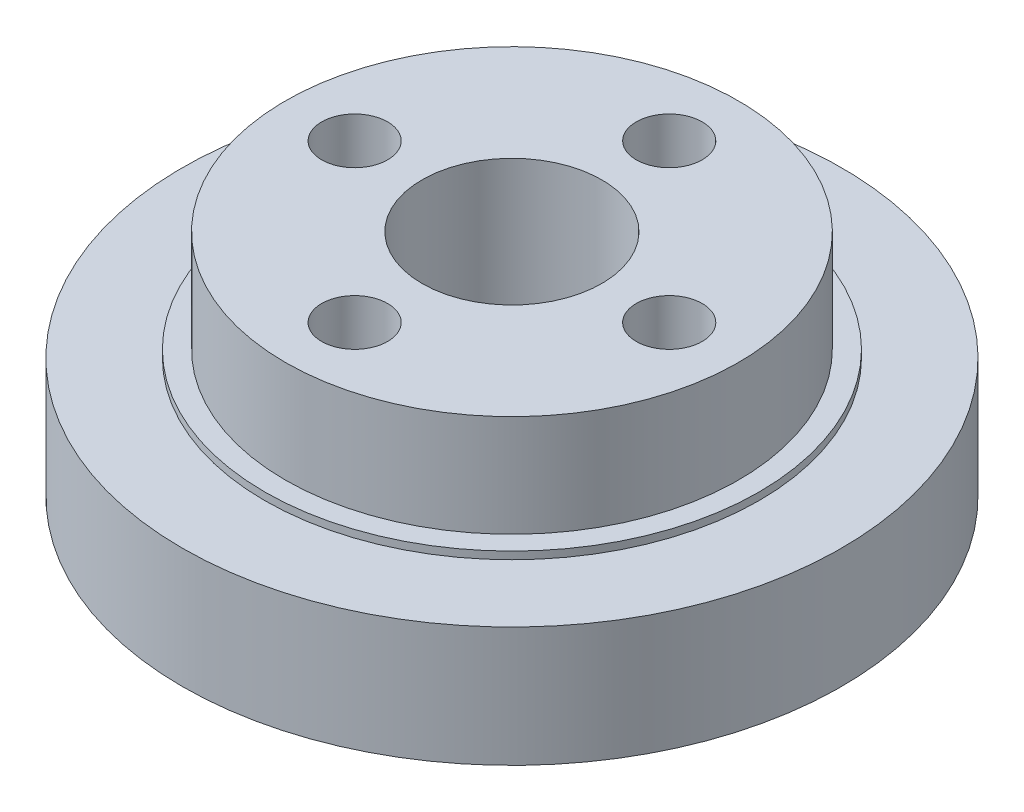
SolidWorks part; units mm, degrees
ref_plane "Front Plane" through (0, 0, 0) normal (0, 0, 1) x (1, 0, 0)
ref_plane "Top Plane" through (0, 0, 0) normal (0, 1, 0) x (1, 0, 0)
ref_plane "Right Plane" through (0, 0, 0) normal (1, 0, 0) x (0, 0, -1)
sketch "Sketch1" plane through (0, 0, 0) normal (0, 1, 0) x (1, 0, 0)
  circle A0 centre (0, 0) radius 22
  dimension "D1" = 44
extrude "Boss-Extrude1" add sketch "Sketch1" along normal blind 8
sketch "Sketch2" plane through (0, 8, 0) normal (0, 1, 0) x (1, 0, 0)
  circle A0 centre (0, 0) radius 16.5
  dimension "D1" = 33
extrude "Boss-Extrude2" add sketch "Sketch2" along normal blind 0.5
sketch "Sketch3" plane through (0, 8.5, 0) normal (0, 1, 0) x (1, 0, 0)
  circle A0 centre (0, 0) radius 15.125
  dimension "D1" = 30.25
extrude "Boss-Extrude3" add sketch "Sketch3" along normal blind 6.8
sketch "Sketch4" plane through (0, 15.3, 0) normal (0, 1, 0) x (1, 0, 0)
  circle A0 centre (0, 0) radius 6
  dimension "D1" = 12
extrude "Cut-Extrude1" cut sketch "Sketch4" against normal through all
sketch "Sketch5" plane through (0, 0, 0) normal (0, 1, 0) x (1, 0, 0)
  line L0 (0, 0) -> (26.2686, 0) construction
  line L1 (-8.415, 0) -> (8.415, 0) construction
  line L2 (0, 0) -> (26.9941, 4.2754) construction
  circle A0 centre (18.2722, 2.894) radius 1.6
  dimension "D2" = 3.2
  dimension "D1" = 9
  dimension "D3" = 18.5
extrude "Cut-Extrude2" cut sketch "Sketch5" along normal blind 7
pattern_circular "CirPattern1" count 6 over 360 about axis through (0, 8, 0) along (0, -1, 0) of "Cut-Extrude2" reverse direction yes
sketch "Sketch6" plane through (0, 15.3, 0) normal (0, 1, 0) x (1, 0, 0)
  line L0 (-8.415, 0) -> (8.415, 0) construction
  circle A0 centre (10.5, 0) radius 2.2
  dimension "D1" = 4.4
  dimension "D2" = 10.5
extrude "Cut-Extrude3" cut sketch "Sketch6" against normal blind 5.5
pattern_circular "CirPattern2" count 4 over 360 about axis through (0, 8, 0) along (0, -1, 0) of "Cut-Extrude3"
equation "\"pin_circle_R\" = 27"
equation "\"ecc\" = 1.5"
equation "\"n_pins\" = 11"
equation "\"pin_d\" = 3"
equation "\"out_pin_R\" = 18.5"
equation "\"disc_clr\" = 0.1"
equation "\"seat_6803\" = 26.1"
equation "\"disc_t\" = 5"
equation "\"out_hole_clr\" = 0.5"
equation "\"boss_17\" = 17.20"
equation "\"rotor_bolt_R\" = 10"
equation "\"m25_clr\" = 2.8"
equation "\"m25_head\" = 5"
equation "\"insert_hole\" = 4.4"
equation "\"csk\" = 0.6"
equation "\"peg_d\" = 3.0"
equation "\"plug_d\" = 8.6"
equation "\"peg_clr\" = 0.3"
equation "\"m3_clr\" = 3.4"
equation "\"m3_head\" = 6.2"
equation "\"pin_press\" = 3.2"
equation "\"hub_30\" = 30.25"
equation "\"hub_short\" = 0.2"
equation "\"m3_tap\" = 2.8"
equation "\"D1@Sketch3\"=\"hub_30\""
equation "\"D1@Boss-Extrude3\"=7-\"hub_short\""
equation "\"D2@Sketch5\"=\"pin_press\""
equation "\"D3@Sketch5\"=\"out_pin_R\""
equation "\"D1@Sketch6\"=\"insert_hole\""
equation "\"seat_6806\" = 42.1"
equation "\"pin_slip\" = 3.3"
equation "\"rear_plate_t\" = 2"
equation "\"motor_ring\" = 40.4"
